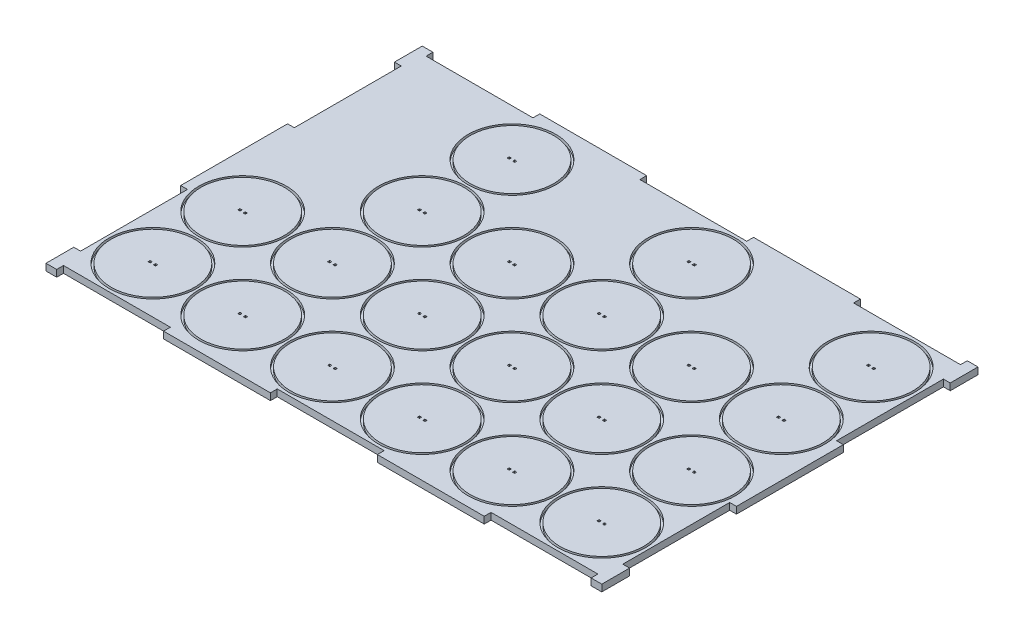
SolidWorks part; units mm, degrees
material "Oak"
ref_plane "Front Plane" through (0, 0, 0) normal (0, 0, 1) x (1, 0, 0)
ref_plane "Top Plane" through (0, 0, 0) normal (0, 1, 0) x (1, 0, 0)
ref_plane "Right Plane" through (0, 0, 0) normal (1, 0, 0) x (0, 0, -1)
sketch "Sketch2" plane through (0, 0, 0) normal (0, 1, 0) x (1, 0, 0)
  line L2 (105, -63) -> (63, -63) construction
  line L3 (105, -63) -> (-105, 63) construction
  line L4 (-105, -63) -> (-105, 63) construction
  line L5 (-105, 63) -> (105, 63) construction
  line L6 (-105, -63) -> (105, 63) construction
  circle A0 centre (105, -63) radius 20
  circle A1 centre (63, -63) radius 20
  circle A2 centre (21, -63) radius 20
  circle A3 centre (-21, -63) radius 20
  circle A4 centre (-63, -63) radius 20
  circle A5 centre (-105, -63) radius 20
  circle A6 centre (63, -21) radius 20
  circle A7 centre (21, -21) radius 20
  circle A8 centre (-21, -21) radius 20
  circle A9 centre (-63, -21) radius 20
  circle A10 centre (-105, -21) radius 20
  circle A11 centre (63, 21) radius 20
  circle A12 centre (21, 21) radius 20
  circle A13 centre (-21, 21) radius 20
  circle A14 centre (-63, 21) radius 20
  circle A17 centre (21, 63) radius 20
  circle A19 centre (-63, 63) radius 20
  circle A21 centre (105, -21) radius 20
  circle A22 centre (105, 21) radius 20
  circle A23 centre (105, 63) radius 20
  circle A24 centre (-105, 63) radius 20
  circle A25 centre (-105, 21) radius 20
  circle A26 centre (-21, 63) radius 20
  circle A27 centre (63, 63) radius 20
  point P0 (0, 0)
  dimension "D1" = 40
  dimension "D2" = 42
  dimension "D6" = 4
  dimension "D4" = 42
  dimension "D5" = 6
sketch "Sketch3" plane through (0, 0, 0) normal (0, 1, 0) x (1, 0, 0)
  line L1 (130, 88) -> (-130, 88)
  line L2 (130, 88) -> (130, -88)
  line L3 (130, -88) -> (-130, -88)
  line L4 (-130, 88) -> (-130, -88)
  line L5 (130, 88) -> (-130, -88) construction
  line L6 (130, -88) -> (-130, 88) construction
  circle A0 centre (-105, -63) radius 20 construction
  point P6 (0, 0)
  dimension "D1" = 25
  dimension "D2" = 25
extrude "Boss-Extrude2" add sketch "Sketch3" along normal mid plane 3.175
sketch "Sketch4" plane through (0, 1.5875, 0) normal (0, 1, 0) x (1, 0, 0)
  line L0 (105, -63) -> (63, -63) construction
  circle A25 centre (63, -63) radius 20.5
  circle A26 centre (105, -63) radius 20.5
  circle A27 centre (105, -63) radius 20.5
  circle A28 centre (105, -63) radius 19.5
  circle A29 centre (105, -63) radius 19.5
  circle A30 centre (63, -63) radius 19.5
  circle A31 centre (21, -63) radius 20.5
  circle A32 centre (21, -63) radius 19.5
  circle A33 centre (-21, -63) radius 20.5
  circle A34 centre (-21, -63) radius 19.5
  circle A35 centre (-63, -63) radius 20.5
  circle A36 centre (-63, -63) radius 19.5
  circle A37 centre (-105, -63) radius 20.5
  circle A38 centre (-105, -63) radius 19.5
  circle A39 centre (63, -21) radius 20.5
  circle A40 centre (63, -21) radius 19.5
  circle A41 centre (21, -21) radius 20.5
  circle A42 centre (21, -21) radius 19.5
  circle A43 centre (-21, -21) radius 20.5
  circle A44 centre (-21, -21) radius 19.5
  circle A45 centre (-63, -21) radius 20.5
  circle A46 centre (-63, -21) radius 19.5
  circle A47 centre (-105, -21) radius 20.5
  circle A48 centre (-105, -21) radius 19.5
  circle A49 centre (63, 21) radius 20.5
  circle A50 centre (63, 21) radius 19.5
  circle A51 centre (21, 21) radius 20.5
  circle A52 centre (21, 21) radius 19.5
  circle A53 centre (-21, 21) radius 20.5
  circle A54 centre (-21, 21) radius 19.5
  circle A55 centre (-63, 21) radius 20.5
  circle A56 centre (-63, 21) radius 19.5
  circle A61 centre (21, 63) radius 20.5
  circle A62 centre (21, 63) radius 19.5
  circle A65 centre (-63, 63) radius 20.5
  circle A66 centre (-63, 63) radius 19.5
  circle A69 centre (105, -21) radius 20.5
  circle A70 centre (105, -21) radius 19.5
  circle A71 centre (105, 21) radius 20.5
  circle A72 centre (105, 21) radius 19.5
  circle A73 centre (105, 63) radius 20.5
  circle A74 centre (105, 63) radius 19.5
  circle A75 centre (-105, 63) radius 20.5 [skipped]
  circle A76 centre (-105, 63) radius 19.5 [skipped]
  circle A77 centre (-105, 21) radius 19.5 [skipped]
  circle A78 centre (-105, 21) radius 20.5 [skipped]
  circle A79 centre (-21, 63) radius 20.5 [skipped]
  circle A80 centre (-21, 63) radius 19.5 [skipped]
  circle A81 centre (63, 63) radius 20.5 [skipped]
  circle A82 centre (63, 63) radius 19.5 [skipped]
  dimension "D3" = 42
  dimension "D1" = 0.5
  dimension "D2" = 0.5
  dimension "D4" = 6
  dimension "D5" = 4
extrude "Cut-Extrude1" cut sketch "Sketch4" against normal blind 1.5
sketch "Sketch5" plane through (0, 1.5875, 0) normal (0, 1, 0) x (1, 0, 0)
  line L0 (85, -63) -> (125, -63) construction
  line L1 (105, -58.1195) -> (105, -66.5107) construction
  line L2 (103.23, -62.5) -> (104.23, -62.5)
  line L3 (103.23, -62.5) -> (103.23, -63.5)
  line L4 (103.23, -63.5) -> (104.23, -63.5)
  line L5 (104.23, -62.5) -> (104.23, -63.5)
  line L6 (103.23, -62.5) -> (104.23, -63.5) construction
  line L7 (103.23, -63.5) -> (104.23, -62.5) construction
  line L8 (106.77, -63.5) -> (105.77, -62.5) construction
  line L9 (106.77, -62.5) -> (105.77, -63.5) construction
  line L10 (105.77, -62.5) -> (105.77, -63.5)
  line L11 (106.77, -63.5) -> (105.77, -63.5)
  line L12 (106.77, -62.5) -> (106.77, -63.5)
  line L13 (106.77, -62.5) -> (105.77, -62.5)
  circle A1 centre (-63, -63) radius 20
  circle A2 centre (-63, -63) radius 20
  circle A3 centre (-21, -63) radius 20
  circle A4 centre (-21, -63) radius 20
  circle A5 centre (21, -63) radius 20
  circle A6 centre (21, -63) radius 20
  circle A7 centre (63, -63) radius 20
  circle A8 centre (63, -63) radius 20
  circle A9 centre (105, -63) radius 20
  circle A10 centre (105, -63) radius 20
  circle A11 centre (21, 21) radius 20
  circle A12 centre (21, 21) radius 20
  circle A13 centre (63, 21) radius 20
  circle A14 centre (63, 21) radius 20
  circle A15 centre (-105, -21) radius 20
  circle A16 centre (-105, -21) radius 20
  circle A17 centre (-63, -21) radius 20
  circle A18 centre (-63, -21) radius 20
  circle A19 centre (-21, -21) radius 20
  circle A20 centre (-21, -21) radius 20
  circle A21 centre (21, -21) radius 20
  circle A22 centre (21, -21) radius 20
  circle A23 centre (63, -21) radius 20
  circle A24 centre (63, -21) radius 20
  circle A25 centre (-105, -63) radius 20
  circle A26 centre (-105, -63) radius 20
  circle A27 centre (-63, 63) radius 20
  circle A28 centre (-63, 63) radius 20
  circle A29 centre (21, 63) radius 20
  circle A30 centre (21, 63) radius 20
  circle A31 centre (-63, 21) radius 20
  circle A32 centre (-63, 21) radius 20
  circle A33 centre (-21, 21) radius 20
  circle A34 centre (-21, 21) radius 20
  circle A35 centre (105, 63) radius 20
  circle A36 centre (105, 63) radius 20
  circle A37 centre (105, 21) radius 20
  circle A38 centre (105, 21) radius 20
  circle A39 centre (105, -21) radius 20
  circle A40 centre (105, -21) radius 20
  point P62 (103.73, -63)
  point P73 (106.27, -63)
  dimension "D21" = 1.27
  dimension "D22" = 1
  dimension "D23" = 1
  dimension "D1" = 0
  dimension "D2" = 0
  dimension "D3" = 0
  dimension "D4" = 0
  dimension "D5" = 0
  dimension "D6" = 0
  dimension "D7" = 0
  dimension "D8" = 0
  dimension "D9" = 0
  dimension "D10" = 0
  dimension "D11" = 0
  dimension "D12" = 0
  dimension "D13" = 0
  dimension "D14" = 0
  dimension "D15" = 0
  dimension "D16" = 0
  dimension "D17" = 0
  dimension "D18" = 0
  dimension "D19" = 0
  dimension "D20" = 0
extrude "Cut-Extrude9" cut sketch "Sketch5" against normal blind 11.5 and the other way blind 11.5 contours L5 L2 L3 L4 | L12 L13 L10 L11 region at (103.73, 1.5875, 63) region at (106.27, 1.5875, 63)
pattern_linear "LPattern1" count 4 spacing 42 along (0, 0, -1) count 6 spacing 42 along (-1, 0, 0) skipping (2, 5), (3, 1), (3, 3), (3, 5) of "Cut-Extrude9"
sketch "Sketch9" plane through (0, 1.5875, 0) normal (0, 1, 0) x (1, 0, 0)
  line L0 (-130, 75) -> (-126.825, 75)
  line L1 (-130, 88) -> (-130, -88) construction
  line L2 (-126.825, 75) -> (-126.825, 25)
  line L3 (-130, -25) -> (-126.825, -25)
  line L4 (-126.825, -25) -> (-126.825, -75)
  line L5 (-126.825, -75) -> (-130, -75)
  line L6 (-130, 0) -> (130, 0) construction
  line L7 (-126.825, 25) -> (-130, 25)
  line L8 (130, 88) -> (-130, 88) construction
  line L9 (-130, -88) -> (130, -88) construction
  line L10 (0, 88) -> (0, -88) construction
  line L11 (126.825, 25) -> (130, 25)
  line L12 (126.825, -75) -> (130, -75)
  line L13 (126.825, -25) -> (126.825, -75)
  line L14 (130, -25) -> (126.825, -25)
  line L15 (126.825, 75) -> (126.825, 25)
  line L16 (130, 75) -> (126.825, 75)
  line L17 (-125, 88) -> (-125, 84.82)
  line L18 (-125, 84.82) -> (-75, 84.82)
  line L19 (-75, 84.82) -> (-75, 88)
  line L20 (-25, 88) -> (-25, 84.82)
  line L21 (-25, 84.82) -> (25, 84.82)
  line L22 (25, 84.82) -> (25, 88)
  line L23 (75, 88) -> (75, 84.82)
  line L24 (75, 84.82) -> (125, 84.82)
  line L25 (125, 84.82) -> (125, 88)
  line L26 (130, -88) -> (130, 88) construction
  line L27 (125, -84.82) -> (125, -88)
  line L28 (75, -84.82) -> (125, -84.82)
  line L29 (75, -88) -> (75, -84.82)
  line L30 (25, -84.82) -> (25, -88)
  line L31 (-25, -84.82) -> (25, -84.82)
  line L32 (-25, -88) -> (-25, -84.82)
  line L33 (-75, -84.82) -> (-75, -88)
  line L34 (-125, -84.82) -> (-75, -84.82)
  line L35 (-125, -88) -> (-125, -84.82)
  line L36 (-130, -75) -> (-130, -25)
  line L37 (-130, 25) -> (-130, 75)
  line L38 (-125, 88) -> (-75, 88)
  line L39 (-25, 88) -> (25, 88)
  line L40 (75, 88) -> (125, 88)
  line L41 (130, 75) -> (130, 25)
  line L42 (130, -25) -> (130, -75)
  line L43 (125, -88) -> (75, -88)
  line L44 (25, -88) -> (-25, -88)
  line L45 (-75, -88) -> (-125, -88)
  line M29 (-130, 88) -> (-130, -88)
  line M30 (-130, -88) -> (130, -88)
  line M31 (130, -88) -> (130, 88)
  line M32 (130, 88) -> (-130, 88)
  dimension "D1" = 50
  dimension "D2" = 50
  dimension "D3" = 13
  dimension "D4" = 50
  dimension "D5" = 13
  dimension "D6" = 5
  dimension "D7" = 50
  dimension "D8" = 3.175
  dimension "D9" = 3.18
  dimension "D10" = 50
  dimension "D11" = 50
  dimension "D12" = 50
  dimension "D13" = 50
  dimension "D14" = 5
ref_axis "Axis2" through (0, 2.0625, 0) along (0, -1, 0)
extrude "Cut-Extrude10" cut sketch "Sketch9" against normal blind 11.5 and the other way through all contours L35 L33 L34 M30 | L5 L4 L3 M29 | L32 L30 L31 M30 | L16 L15 L11 M31 | L24 L25 L23 M32 | L21 L22 L20 M32 | L7 L2 L0 M29 | L18 L19 L17 M32 | L29 L27 L28 M30 | L14 L13 L12 M31 region at (-128.4125, 1.5875, -50) region at (-128.4125, 1.5875, 50) region at (-100, 1.5875, -86.41) region at (0, 1.5875, -86.41) region at (-100, 1.5875, 86.41) region at (100, 1.5875, -86.41) region at (0, 1.5875, 86.41) region at (100, 1.5875, 86.41) region at (128.4125, 1.5875, -50) region at (128.4125, 1.5875, 50)
